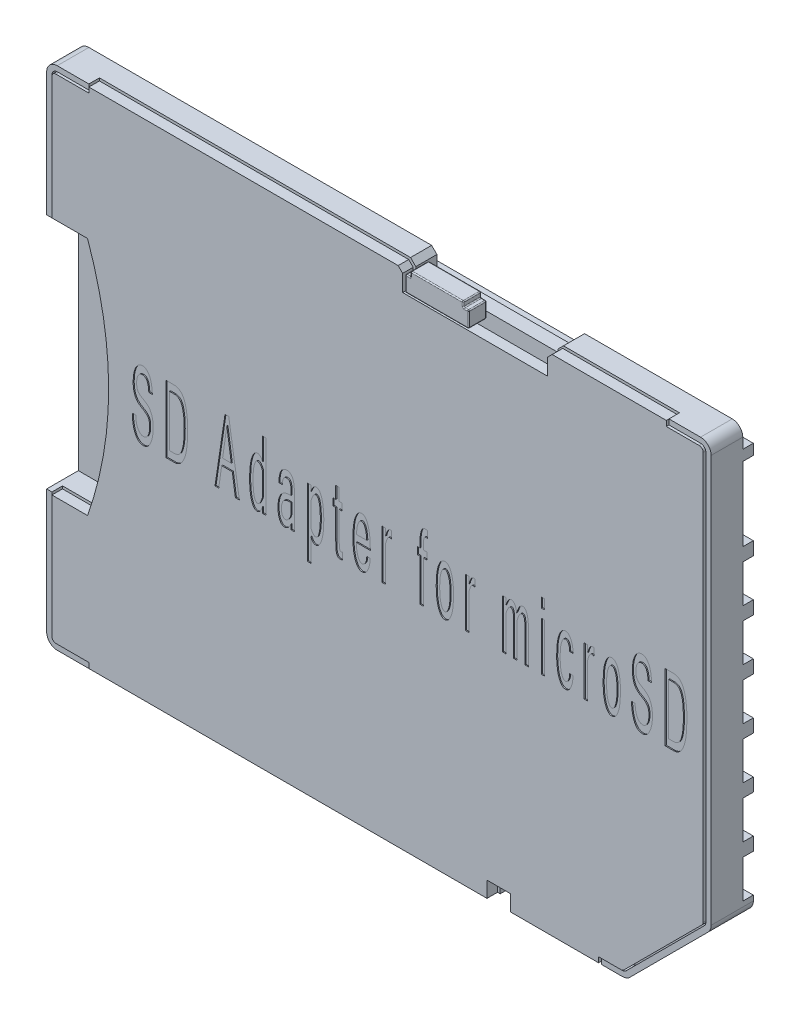
SolidWorks part; units mm, degrees
ref_plane "Front Plane" through (0, 0, 0) normal (0, 0, 1) x (1, 0, 0)
ref_plane "Top Plane" through (0, 0, 0) normal (0, 1, 0) x (1, 0, 0)
ref_plane "Right Plane" through (0, 0, 0) normal (1, 0, 0) x (0, 0, -1)
sketch "Sketch1" plane through (0, 0, 0) normal (0, 0, 1) x (1, 0, 0)
  line L0 (6.25, 0) -> (6.25, 0.75)
  line L1 (15.75, 24) -> (15.75, 4)
  line L2 (-15.75, 0) -> (-15.75, 24)
  line L3 (11.75, 0) -> (6.25, 0)
  line L4 (6.25, 0.75) -> (5.25, 0.75)
  line L5 (15.75, 4) -> (11.75, 0)
  line L6 (5.25, 0.75) -> (5.25, 0)
  line L7 (5.25, 0) -> (-15.75, 0)
  line L8 (-15.75, 24) -> (15.75, 24)
extrude "Boss-Extrude1" add sketch "Sketch1" along normal blind 2
fillet "Fillet1" radius 0.5 5 edges at (-15.75, 0, 1) (-15.75, 24, 1) (15.75, 24, 1) (11.75, 0, 1) (15.75, 4, 1)
sketch "Sketch2" plane through (0, 0, 0) normal (0, 0, -1) x (-1, 0, 0)
  line L0 (15.75, 23) -> (15.75, 23.5)
  line L2 (0, 23) -> (15.75, 23)
  line L3 (15.75, 23.5) -> (15.75, 0.5) construction
  line L4 (0, 23) -> (-15.75, 23)
  line L5 (-15.75, 4.2071) -> (-15.75, 23.5) construction
  line L6 (-15.75, 23) -> (-15.75, 23.5)
  line L10 (15.25, 24) -> (-15.25, 24)
  line L11 (15.25, 24) -> (-15.25, 24)
  arc A6 (15.75, 23.5) -> (15.25, 24) centre (15.25, 23.5) ccw
  arc A7 (-15.25, 24) -> (-15.75, 23.5) centre (-15.25, 23.5) ccw
  arc A8 (15.75, 23.5) -> (15.25, 24) centre (15.25, 23.5) ccw
  arc A9 (-15.25, 24) -> (-15.75, 23.5) centre (-15.25, 23.5) ccw
  dimension "D1" = 0
extrude "Cut-Extrude1" cut sketch "Sketch2" against normal blind 0.5
sketch "Sketch3" plane through (0, 0, 0) normal (0, 0, -1) x (-1, 0, 0)
  line L1 (0, 0.75) -> (15.75, 0.75)
  line L2 (15.75, 23) -> (15.75, 0.5) construction
  line L3 (15.75, 0.75) -> (15.75, 0.5)
  line L4 (0, 0.75) -> (-12.5, 0.75)
  line L5 (-11.8964, 0.1464) -> (-15.6036, 3.8536) construction
  line L6 (-12.5, 0.75) -> (-11.8964, 0.1464)
  line L18 (15.25, 0) -> (-5.25, 0)
  line L19 (15.25, 0) -> (-5.25, 0)
  line L20 (-6.25, 0) -> (-5.25, 0)
  line L21 (-11.5429, 0) -> (-6.25, 0)
  line L22 (-11.5429, 0) -> (-6.25, 0)
  arc A16 (15.25, 0) -> (15.75, 0.5) centre (15.25, 0.5) ccw
  arc A17 (15.25, 0) -> (15.75, 0.5) centre (15.25, 0.5) ccw
  arc A20 (-11.8964, 0.1464) -> (-11.5429, 0) centre (-11.5429, 0.5) ccw
  arc A21 (-11.8964, 0.1464) -> (-11.5429, 0) centre (-11.5429, 0.5) ccw
  dimension "D1" = 0
  dimension "D2" = 0
extrude "Cut-Extrude2" cut sketch "Sketch3" against normal blind 0.5
sketch "Sketch4" plane through (0, 0, 2) normal (0, 0, 1) x (1, 0, 0)
  line L0 (1.25, 23.25) -> (8, 23.25)
  line L1 (1.25, 24) -> (1.25, 23.25)
  line L2 (15.25, 24) -> (-15.25, 24) construction
  line L3 (8, 23.25) -> (8, 24)
  line L4 (1.25, 24) -> (8, 24)
extrude "Cut-Extrude3" cut sketch "Sketch4" against normal blind 1.5
chamfer "Chamfer1" distance 0.25 angle 45 2 edges at (8, 24, 1.25) (1.25, 24, 1.25)
sketch "Sketch5" plane through (0, 0, 0) normal (0, 0, -1) x (-1, 0, 0)
  line L0 (-15.75, 23) -> (-15.75, 22.5)
  line L1 (-15.75, 4.2071) -> (-15.75, 23) construction
  line L2 (-15.75, 22.5) -> (-10, 22.5)
  line L3 (-10, 22.5) -> (-10, 19)
  line L4 (-10, 19) -> (-15.75, 19)
  line L5 (-15.75, 19) -> (-15.75, 22.5)
  line M5 (-15.75, 23) -> (-15.75, 4.2071)
extrude "Cut-Extrude4" cut sketch "Sketch5" against normal blind 0.5 contours L4 L3 L2 M5 region at (12.875, 20.75, 0)
sketch "Sketch9" plane through (0, 0, 0) normal (0, 0, -1) x (-1, 0, 0)
  line L0 (-15.75, 18.375) -> (-15.75, 16.575)
  line L1 (-15.75, 4.2071) -> (-15.75, 19) construction
  line L2 (-15.75, 18.375) -> (-10, 18.375)
  line L3 (-10, 18.375) -> (-10, 16.575)
  line L4 (-10, 16.575) -> (-15.75, 16.575)
  line L5 (-15.75, 6.25) -> (-15.75, 4.45)
  line L6 (-15.75, 15.95) -> (-10, 15.95)
  line L7 (-10, 15.95) -> (-10, 14.15)
  line L8 (-10, 14.15) -> (-15.75, 14.15)
  line L9 (-15.75, 8.675) -> (-15.75, 6.875)
  line L10 (-15.75, 13.525) -> (-10, 13.525)
  line L11 (-10, 13.525) -> (-10, 11.725)
  line L12 (-10, 11.725) -> (-15.75, 11.725)
  line L13 (-15.75, 11.1) -> (-15.75, 9.3)
  line L14 (-15.75, 11.1) -> (-10, 11.1)
  line L15 (-10, 11.1) -> (-10, 9.3)
  line L16 (-10, 9.3) -> (-15.75, 9.3)
  line L17 (-15.75, 13.525) -> (-15.75, 11.725)
  line L18 (-15.75, 8.675) -> (-10, 8.675)
  line L19 (-10, 8.675) -> (-10, 6.875)
  line L20 (-10, 6.875) -> (-15.75, 6.875)
  line L21 (-15.75, 15.95) -> (-15.75, 14.15)
  line L22 (-15.75, 6.25) -> (-10, 6.25)
  line L23 (-10, 6.25) -> (-10, 4.45)
  line L24 (-10, 4.45) -> (-15.75, 4.45)
  line L26 (-15.6, 3.85) -> (-7.75, 3.85)
  line L27 (-7.75, 3.85) -> (-7.75, 2.05)
  line L28 (-7.75, 2.05) -> (-13.8, 2.05)
  line L29 (-12.5, 0.75) -> (-15.6036, 3.8536) construction
  line L30 (-13.8, 2.05) -> (-15.6, 3.85)
  dimension "D1" = 1.8
  dimension "D2" = 1.8
  dimension "D3" = 1.8
  dimension "D4" = 1.8
  dimension "D5" = 1.8
  dimension "D6" = 1.8
  dimension "D7" = 0.625
  dimension "D8" = 0.625
  dimension "D9" = 0.625
  dimension "D10" = 0.625
  dimension "D11" = 0.625
extrude "Cut-Extrude7" cut sketch "Sketch9" against normal blind 0.5
sketch "Sketch10" plane through (0, 0, 0.5) normal (0, 0, -1) x (-1, 0, 0)
  line L6 (-10.125, 22.5) -> (-10.125, 19)
  line L7 (-10.125, 22.375) -> (-10.125, 19.125)
  line L9 (-10.125, 16.575) -> (-10.125, 18.375)
  line L10 (-10.125, 16.7) -> (-10.125, 18.25)
  line L12 (-10.125, 14.15) -> (-10.125, 15.95)
  line L13 (-10.125, 14.275) -> (-10.125, 15.825)
  line L15 (-10.125, 11.725) -> (-10.125, 13.525)
  line L16 (-10.125, 11.85) -> (-10.125, 13.4)
  line L18 (-10.125, 9.3) -> (-10.125, 11.1)
  line L19 (-10.125, 9.425) -> (-10.125, 10.975)
  line L21 (-10.125, 6.875) -> (-10.125, 8.675)
  line L22 (-10.125, 7) -> (-10.125, 8.55)
  line L24 (-10.125, 4.45) -> (-10.125, 6.25)
  line L25 (-10.125, 4.575) -> (-10.125, 6.125)
  line L26 (-14.125, 22.375) -> (-14.125, 19.125)
  line L27 (-7.875, 2.05) -> (-7.875, 3.85)
  line L28 (-7.875, 2.175) -> (-7.875, 3.725)
  line L29 (-14.125, 16.7) -> (-14.125, 18.25)
  line L30 (-14.125, 14.275) -> (-14.125, 15.825)
  line L31 (-14.125, 11.85) -> (-14.125, 13.4)
  line L32 (-14.125, 9.425) -> (-14.125, 10.975)
  line L33 (-14.125, 7) -> (-14.125, 8.55)
  line L34 (-14.125, 4.575) -> (-14.125, 6.125)
  line L37 (-15.75, 22.375) -> (-10, 22.375)
  line L38 (-14.125, 22.375) -> (-10.125, 22.375)
  line L40 (-10, 19.125) -> (-15.75, 19.125)
  line L41 (-10.125, 19.125) -> (-14.125, 19.125)
  line L43 (-10, 18.25) -> (-15.75, 18.25)
  line L44 (-10.125, 18.25) -> (-14.125, 18.25)
  line L46 (-15.75, 16.7) -> (-10, 16.7)
  line L47 (-14.125, 16.7) -> (-10.125, 16.7)
  line L52 (-10, 15.825) -> (-15.75, 15.825)
  line L53 (-10.125, 15.825) -> (-14.125, 15.825)
  line L55 (-15.75, 14.275) -> (-10, 14.275)
  line L56 (-14.125, 14.275) -> (-10.125, 14.275)
  line L58 (-10, 13.4) -> (-15.75, 13.4)
  line L59 (-10.125, 13.4) -> (-14.125, 13.4)
  line L61 (-15.75, 11.85) -> (-10, 11.85)
  line L62 (-14.125, 11.85) -> (-10.125, 11.85)
  line L64 (-10, 10.975) -> (-15.75, 10.975)
  line L65 (-10.125, 10.975) -> (-14.125, 10.975)
  line L67 (-15.75, 9.425) -> (-10, 9.425)
  line L68 (-14.125, 9.425) -> (-10.125, 9.425)
  line L70 (-10, 8.55) -> (-15.75, 8.55)
  line L71 (-10.125, 8.55) -> (-14.125, 8.55)
  line L73 (-15.75, 7) -> (-10, 7)
  line L74 (-14.125, 7) -> (-10.125, 7)
  line L76 (-10, 6.125) -> (-15.75, 6.125)
  line L77 (-10.125, 6.125) -> (-14.125, 6.125)
  line L79 (-15.75, 4.575) -> (-10, 4.575)
  line L80 (-14.125, 4.575) -> (-10.125, 4.575)
  line L82 (-7.75, 3.725) -> (-15.6, 3.725)
  line L83 (-7.875, 3.725) -> (-11.625, 3.725)
  line L84 (-11.625, 2.175) -> (-11.625, 3.725)
  line L85 (-13.8, 2.175) -> (-7.75, 2.175)
  line L86 (-11.625, 2.175) -> (-7.875, 2.175)
  line L88 (-11.625, 2.05) -> (-11.625, 3.85) construction
  line L89 (-7.875, 2.05) -> (-7.875, 3.85) construction
  line L90 (-14.125, 4.45) -> (-14.125, 6.25) construction
  line L91 (-10.125, 4.45) -> (-10.125, 6.25) construction
  line L92 (-14.125, 6.875) -> (-14.125, 8.675) construction
  line L93 (-10.125, 6.875) -> (-10.125, 8.675) construction
  line L94 (-14.125, 9.3) -> (-14.125, 11.1) construction
  line L95 (-10.125, 9.3) -> (-10.125, 11.1) construction
  line L96 (-14.125, 11.725) -> (-14.125, 13.525) construction
  line L97 (-10.125, 11.725) -> (-10.125, 13.525) construction
  line L98 (-14.125, 14.15) -> (-14.125, 15.95) construction
  line L99 (-10.125, 14.15) -> (-10.125, 15.95) construction
  line L100 (-14.125, 16.575) -> (-14.125, 18.375) construction
  line L101 (-10.125, 16.575) -> (-10.125, 18.375) construction
  line L102 (-14.125, 22.5) -> (-14.125, 19) construction
  line L103 (-10.125, 22.5) -> (-10.125, 19) construction
  dimension "D1" = 0.125
  dimension "D2" = 0.125
  dimension "D3" = 0.125
  dimension "D4" = 0.125
  dimension "D5" = 0.125
  dimension "D6" = 0.125
  dimension "D7" = 0.125
  dimension "D8" = 0.125
  dimension "D9" = 4
  dimension "D10" = 4
  dimension "D11" = 0.125
  dimension "D12" = 0.125
  dimension "D13" = 0.125
  dimension "D14" = 0.125
  dimension "D15" = 0.125
  dimension "D16" = 0.125
  dimension "D17" = 0.125
  dimension "D18" = 0.125
  dimension "D19" = 0.125
  dimension "D20" = 0.125
  dimension "D21" = 0.125
  dimension "D22" = 0.125
  dimension "D23" = 0.125
  dimension "D24" = 0.125
  dimension "D25" = 0.125
  dimension "D26" = 0.125
  dimension "D27" = 3.75
extrude "Boss-Extrude2" add sketch "Sketch10" along normal blind 0.05 separate body
sketch "Sketch11" plane through (0, 23.25, 0) normal (0, 1, 0) x (1, 0, 0)
  line L0 (8, -1.9) -> (8, -1.15)
  line L1 (8, -0.5) -> (8, -2) construction
  line L2 (8, -1.9) -> (1.25, -1.9)
  line L3 (1.25, -0.5) -> (1.25, -2) construction
  line L4 (1.25, -1.9) -> (1.25, -1.15)
  line L5 (1.25, -0.5) -> (1.25, -2) construction
  line L6 (1.25, -1.15) -> (8, -1.15)
  line L7 (8, -2) -> (8, -0.5) construction
  line L8 (8, -1.15) -> (8, -1.9)
  line M4 (8, -2) -> (8, -0.5)
  line M6 (1.25, -0.5) -> (1.25, -2)
extrude "Cut-Extrude8" cut sketch "Sketch11" against normal blind 0.25 contours L6 L2 M6 M4 region at (4.625, 23.25, 1.525)
sketch "Sketch12" plane through (0, 0, 2) normal (0, 0, 1) x (1, 0, 0)
  line L15 (-15.75, 6.375) -> (-15.75, 17.625)
  line L16 (-15.75, 6.375) -> (-13.75, 6.375)
  line L17 (-15.75, 17.625) -> (-13.75, 17.625)
  spline S0 degree 2 poles (-13.75, 6.375) (-12.25, 12) (-13.75, 17.625) knots 0 0 0 1 1 1
extrude "Cut-Extrude9" cut sketch "Sketch12" against normal blind 1.5
sketch "Sketch13" plane through (0, 0, 2) normal (0, 0, 1) x (1, 0, 0)
  line L2 (-15.5, 23.5) -> (-15.5, 17.625)
  line L3 (-15.5, 23.5) -> (-15.5, 17.625)
  line L4 (-13.75, 24) -> (1, 24)
  line L5 (1, 23.75) -> (-15.25, 23.75)
  line L6 (-13.75, 23.75) -> (-15.25, 23.75)
  line L7 (-13.75, 23.75) -> (-13.75, 24)
  line L8 (1, 24) -> (-15.25, 24) construction
  line L9 (1, 24) -> (1.25, 23.75)
  line L10 (1.25, 23.75) -> (1.25, 23.25)
  line L11 (1.25, 23.25) -> (8, 23.25)
  line L12 (8, 23.25) -> (8, 23.75)
  line L13 (8, 23.75) -> (8.25, 24)
  line L16 (15.5, 4.2071) -> (15.5, 23.5)
  line L17 (15.5, 4.2071) -> (15.5, 23.5)
  line L19 (11.7197, 0.3232) -> (15.4268, 4.0303)
  line L20 (11.7197, 0.3232) -> (15.4268, 4.0303)
  line L38 (11.5429, 0.25) -> (10.5429, 0.25)
  line L39 (10.5429, 0.25) -> (10.5429, 0)
  line L40 (6.25, 0) -> (11.5429, 0) construction
  line L41 (10.5429, 0) -> (6.25, 0)
  line L42 (6.25, 0) -> (6.25, 0.75)
  line L43 (6.25, 0.75) -> (5.25, 0.75)
  line L44 (5.25, 0.75) -> (5.25, 0)
  line L46 (-13.75, 0) -> (5.25, 0)
  line L47 (-15.5, 6.375) -> (-15.5, 0.5)
  line L48 (-15.5, 6.375) -> (-15.5, 0.5)
  line L49 (-13.75, 0.25) -> (-13.75, 0)
  line L50 (-15.25, 0) -> (5.25, 0) construction
  line L51 (-15.25, 0.25) -> (-13.75, 0.25)
  line L52 (13.75, 24) -> (8.25, 24)
  line L53 (13.75, 23.75) -> (13.75, 24)
  line L54 (15.25, 24) -> (8.25, 24) construction
  line L55 (15.25, 23.75) -> (13.75, 23.75)
  line L58 (-13.75, 17.625) -> (-15.75, 17.625)
  line L59 (-13.75, 17.625) -> (-15.5, 17.625)
  line L61 (-15.75, 6.375) -> (-13.75, 6.375)
  line L62 (-15.5, 6.375) -> (-13.75, 6.375)
  arc A2 (-15.25, 23.75) -> (-15.5, 23.5) centre (-15.25, 23.5) ccw
  arc A3 (-15.25, 23.75) -> (-15.5, 23.5) centre (-15.25, 23.5) ccw
  arc A5 (15.5, 23.5) -> (15.25, 23.75) centre (15.25, 23.5) ccw
  arc A6 (15.5, 23.5) -> (15.25, 23.75) centre (15.25, 23.5) ccw
  arc A8 (15.4268, 4.0303) -> (15.5, 4.2071) centre (15.25, 4.2071) ccw
  arc A9 (15.4268, 4.0303) -> (15.5, 4.2071) centre (15.25, 4.2071) ccw
  arc A16 (11.5429, 0.25) -> (11.7197, 0.3232) centre (11.5429, 0.5) ccw
  arc A17 (11.5429, 0.25) -> (11.7197, 0.3232) centre (11.5429, 0.5) ccw
  arc A19 (-15.5, 0.5) -> (-15.25, 0.25) centre (-15.25, 0.5) ccw
  arc A20 (-15.5, 0.5) -> (-15.25, 0.25) centre (-15.25, 0.5) ccw
  parabola Q3 (-13.75, 6.375) -> (-13.75, 17.625) focus (-23.5469, 12) apex (-13, 12)
  parabola Q4 (-13.75, 6.375) -> (-13.75, 17.625) focus (-23.5469, 12) apex (-13, 12)
  dimension "D4" = 0.25
  dimension "D9" = 0.25
  dimension "D11" = 0
  dimension "D1" = 0.25
  dimension "D2" = 0.25
  dimension "D3" = 0.25
  dimension "D5" = 0.25
  dimension "D6" = 0.25
  dimension "D7" = 0.25
  dimension "D8" = 0.25
  dimension "D10" = 0.25
  dimension "D12" = 0
  dimension "D13" = 0
extrude "Cut-Extrude11" cut sketch "Sketch13" against normal blind 0.5
sketch "Sketch14" plane through (0, 0, 1.5) normal (0, 0, 1) x (1, 0, 0)
  line L0 (-13.75, 17.625) -> (-3.75, 17.625)
  line L1 (-3.75, 17.625) -> (-3.75, 6.375)
  line L2 (-13.75, 6.375) -> (-3.75, 6.375)
  parabola Q2 (-13.75, 6.375) -> (-13.75, 17.625) focus (-23.5469, 12) apex (-13, 12)
  parabola Q3 (-13.75, 6.375) -> (-13.75, 17.625) focus (-23.5469, 12) apex (-13, 12)
  dimension "D1" = 0
extrude "Cut-Extrude12" cut sketch "Sketch14" against normal blind 1
ref_plane "Plane1" through (0, 0, 1.5625) normal (0, 0, 1) x (1, 0, 0)
sketch "Sketch16" plane through (0, 0, 1.5625) normal (0, 0, 1) x (1, 0, 0)
  line L54 (-15.4375, 17.6875) -> (-3.6875, 17.6875)
  line L55 (-3.6875, 17.6875) -> (-3.6875, 6.3125)
  line L56 (-3.6875, 6.3125) -> (-15.4375, 6.3125)
  line L57 (-15.4375, 6.3125) -> (-15.4375, 0.5)
  line L58 (-15.25, 0.3125) -> (-13.6875, 0.3125)
  line L59 (-13.6875, 0.3125) -> (-13.6875, 0.0625)
  line L60 (-13.6875, 0.0625) -> (5.1875, 0.0625)
  line L61 (5.1875, 0.0625) -> (5.1875, 0.8125)
  line L62 (5.1875, 0.8125) -> (6.3125, 0.8125)
  line L63 (6.3125, 0.8125) -> (6.3125, 0.0625)
  line L64 (6.3125, 0.0625) -> (10.4804, 0.0625)
  line L65 (10.4804, 0.0625) -> (10.4804, 0.3125)
  line L66 (10.4804, 0.3125) -> (11.5429, 0.3125)
  line L67 (11.6755, 0.3674) -> (15.3826, 4.0745)
  line L68 (15.4375, 4.2071) -> (15.4375, 23.5)
  line L69 (15.25, 23.6875) -> (13.6875, 23.6875)
  line L70 (13.6875, 23.6875) -> (13.6875, 23.9375)
  line L71 (13.6875, 23.9375) -> (8.2759, 23.9375)
  line L72 (8.2759, 23.9375) -> (8.0625, 23.7241)
  line L73 (8.0625, 23.7241) -> (8.0625, 22.9375)
  line L74 (8.0625, 22.9375) -> (1.1875, 22.9375)
  line L75 (1.1875, 22.9375) -> (1.1875, 23.7241)
  line L76 (1.1875, 23.7241) -> (0.9741, 23.9375)
  line L77 (0.9741, 23.9375) -> (-13.6875, 23.9375)
  line L78 (-13.6875, 23.9375) -> (-13.6875, 23.6875)
  line L79 (-13.6875, 23.6875) -> (-15.25, 23.6875)
  line L80 (-15.4375, 23.5) -> (-15.4375, 17.6875)
  line L81 (-15.4375, 17.6875) -> (-13.75, 17.6875)
  line L83 (-13.75, 6.3125) -> (-15.4375, 6.3125)
  line L84 (-15.4375, 6.3125) -> (-15.4375, 0.5)
  line L85 (-15.25, 0.3125) -> (-13.6875, 0.3125)
  line L86 (-13.6875, 0.3125) -> (-13.6875, 0.0625)
  line L87 (-13.6875, 0.0625) -> (5.1875, 0.0625)
  line L88 (5.1875, 0.0625) -> (5.1875, 0.8125)
  line L89 (5.1875, 0.8125) -> (6.3125, 0.8125)
  line L90 (6.3125, 0.8125) -> (6.3125, 0.0625)
  line L91 (6.3125, 0.0625) -> (10.4804, 0.0625)
  line L92 (10.4804, 0.0625) -> (10.4804, 0.3125)
  line L93 (10.4804, 0.3125) -> (11.5429, 0.3125)
  line L94 (11.6755, 0.3674) -> (15.3826, 4.0745)
  line L95 (15.4375, 4.2071) -> (15.4375, 23.5)
  line L96 (15.25, 23.6875) -> (13.6875, 23.6875)
  line L97 (13.6875, 23.6875) -> (13.6875, 23.9375)
  line L98 (13.6875, 23.9375) -> (8.2759, 23.9375)
  line L99 (8.2759, 23.9375) -> (8.0625, 23.7241)
  line L100 (8.0625, 23.7241) -> (8.0625, 22.9375)
  line L101 (8.0625, 22.9375) -> (1.1875, 22.9375)
  line L102 (1.1875, 22.9375) -> (1.1875, 23.7241)
  line L103 (1.1875, 23.7241) -> (0.9741, 23.9375)
  line L104 (0.9741, 23.9375) -> (-13.6875, 23.9375)
  line L105 (-13.6875, 23.9375) -> (-13.6875, 23.6875)
  line L106 (-13.6875, 23.6875) -> (-15.25, 23.6875)
  line L107 (-15.4375, 23.5) -> (-15.4375, 17.6875)
  arc A10 (-15.4375, 0.5) -> (-15.25, 0.3125) centre (-15.25, 0.5) ccw
  arc A11 (11.5429, 0.3125) -> (11.6755, 0.3674) centre (11.5429, 0.5) ccw
  arc A12 (15.3826, 4.0745) -> (15.4375, 4.2071) centre (15.25, 4.2071) ccw
  arc A13 (15.4375, 23.5) -> (15.25, 23.6875) centre (15.25, 23.5) ccw
  arc A14 (-15.25, 23.6875) -> (-15.4375, 23.5) centre (-15.25, 23.5) ccw
  arc A15 (-15.4375, 0.5) -> (-15.25, 0.3125) centre (-15.25, 0.5) ccw
  arc A16 (11.5429, 0.3125) -> (11.6755, 0.3674) centre (11.5429, 0.5) ccw
  arc A17 (15.3826, 4.0745) -> (15.4375, 4.2071) centre (15.25, 4.2071) ccw
  arc A18 (15.4375, 23.5) -> (15.25, 23.6875) centre (15.25, 23.5) ccw
  arc A19 (-15.25, 23.6875) -> (-15.4375, 23.5) centre (-15.25, 23.5) ccw
  spline S0 degree 2 poles (-13.75, 6.3125) (-11.75, 12) (-13.75, 17.6875) knots 0 0 0 1 1 1
  dimension "D1" = 0.0625
extrude "Boss-Extrude3" add sketch "Sketch16" along normal blind 0.5 separate body
sketch "Sketch19" plane through (0, 0, 2.0625) normal (0, 0, 1) x (1, 0, 0)
  text T0 "SD Adapter for microSD" font "Microsoft Sans Serif" height 3.175
extrude "Cut-Extrude13" cut sketch "Sketch19" against normal blind 0.05
sketch "Sketch20" plane through (0, 23, 0) normal (0, 1, 0) x (1, 0, 0)
  line L8 (1.25, -1.15) -> (1.25, -1.5)
  line L9 (1.25, -1.5) -> (8, -1.5)
  line L10 (8, -1.5) -> (8, -1.15)
  line L11 (8, -1.15) -> (1.25, -1.15)
  line L12 (1.25, -1.15) -> (1.25, -1.5)
  line L13 (1.25, -1.5) -> (8, -1.5)
  line L14 (8, -1.5) -> (8, -1.15)
  line L15 (8, -1.15) -> (1.25, -1.15)
  dimension "D1" = 0
extrude "Cut-Extrude14" cut sketch "Sketch20" against normal blind 1
ref_plane "Plane2" through (0, 23, 0) normal (0, 1, 0) x (1, 0, 0)
sketch "Sketch22" plane through (0, 23, 0) normal (0, 1, 0) x (1, 0, 0)
  line L2 (1.3125, -1.15) -> (1.3125, -1.5)
  line L3 (1.3125, -1.2125) -> (1.3125, -1.5)
  line L4 (1.3125, -1.5) -> (1.3125, -2.0625)
  line L5 (8, -1.2125) -> (1.25, -1.2125)
  line L6 (4.3125, -1.2125) -> (1.3125, -1.2125)
  line L7 (8.0625, -2.0625) -> (1.1875, -2.0625) construction
  line L8 (1.3125, -2.0625) -> (4.3125, -2.0625)
  line L9 (4.3125, -2.0625) -> (4.3125, -1.2125)
  dimension "D1" = 0.0625
  dimension "D2" = 0.0625
extrude "Boss-Extrude4" add sketch "Sketch22" along normal blind 1 separate body
sketch "Sketch23" plane through (0, 0, 2.0625) normal (0, 0, 1) x (1, 0, 0)
  line L1 (1.3125, 24) -> (1.5625, 24)
  line L2 (1.3125, 24) -> (1.3125, 23.75)
  line L3 (1.3125, 23.75) -> (1.5625, 23.75)
  line L4 (1.5625, 24) -> (1.5625, 23.75)
  line L5 (4.3125, 24) -> (4.0625, 24)
  line L6 (4.3125, 24) -> (4.3125, 23.75)
  line L7 (4.3125, 23.75) -> (4.0625, 23.75)
  line L8 (4.0625, 24) -> (4.0625, 23.75)
extrude "Cut-Extrude15" cut sketch "Sketch23" against normal blind 1
fillet "Fillet3" radius 0.05 24 edges at (2.8125, 23, 1.2125) (1.3125, 23, 1.6375) (1.3125, 23.375, 1.2125) (1.4375, 23.75, 1.2125) (1.3125, 23.75, 1.6375) (1.5625, 23.875, 1.2125) (1.5625, 23.75, 1.6375) (2.8125, 24, 1.2125) (1.5625, 24, 1.6375) (4.3125, 23, 1.6375) (4.3125, 23.375, 1.2125) (4.0625, 23.875, 1.2125) (4.0625, 24, 1.6375) (4.1875, 23.75, 1.2125) (4.3125, 23.75, 1.6375) (4.0625, 23.75, 1.6375) (4.0625, 23.875, 2.0625) (4.1875, 23.75, 2.0625) (4.3125, 23.375, 2.0625) (2.8125, 23, 2.0625) (1.3125, 23.375, 2.0625) (1.4375, 23.75, 2.0625) (1.5625, 23.875, 2.0625) (2.8125, 24, 2.0625)
